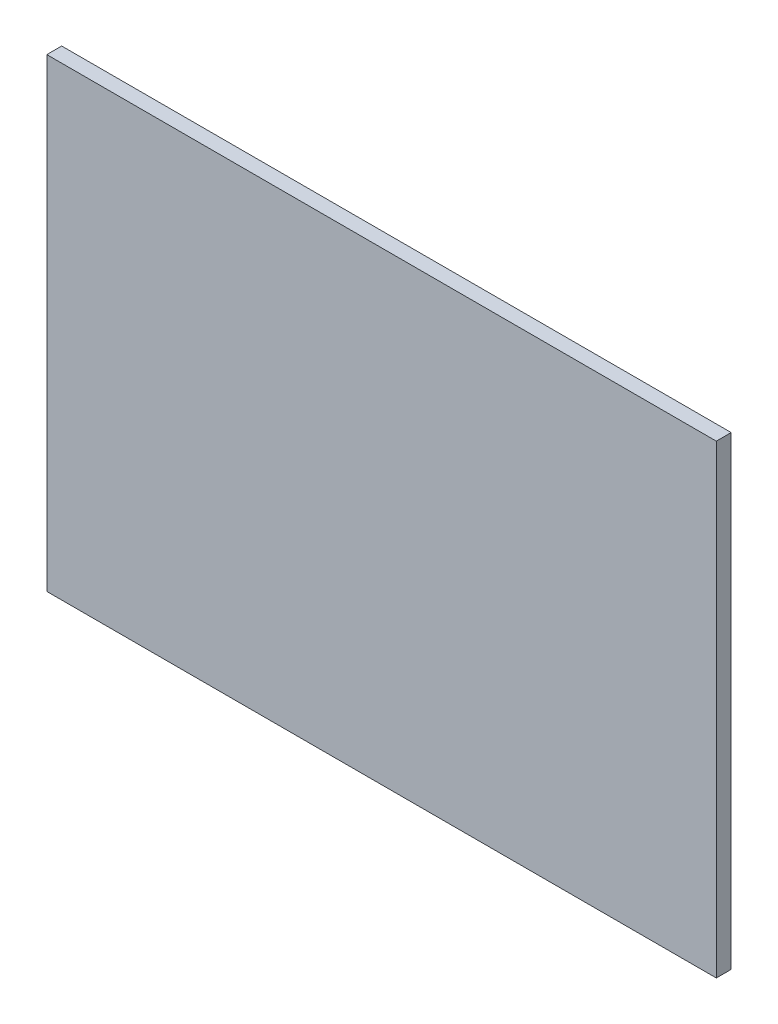
SolidWorks part; units mm, degrees
ref_plane "Alzado" through (0, 0, 0) normal (0, 0, 1) x (1, 0, 0)
ref_plane "Planta" through (0, 0, 0) normal (0, 1, 0) x (1, 0, 0)
ref_plane "Vista lateral" through (0, 0, 0) normal (1, 0, 0) x (0, 0, -1)
sketch "Croquis1" plane through (0, 0, 0) normal (0, 0, 1) x (1, 0, 0)
  line L1 (90, -62.5) -> (-90, -62.5)
  line L2 (90, -62.5) -> (90, 62.5)
  line L3 (90, 62.5) -> (-90, 62.5)
  line L4 (-90, -62.5) -> (-90, 62.5)
  line L5 (90, -62.5) -> (-90, 62.5) construction
  line L6 (90, 62.5) -> (-90, -62.5) construction
  point P0 (0, 0)
  dimension "D1" = 180
  dimension "D2" = 125
extrude "Saliente-Extruir1" add sketch "Croquis1" along normal blind 2 and the other way blind 2
